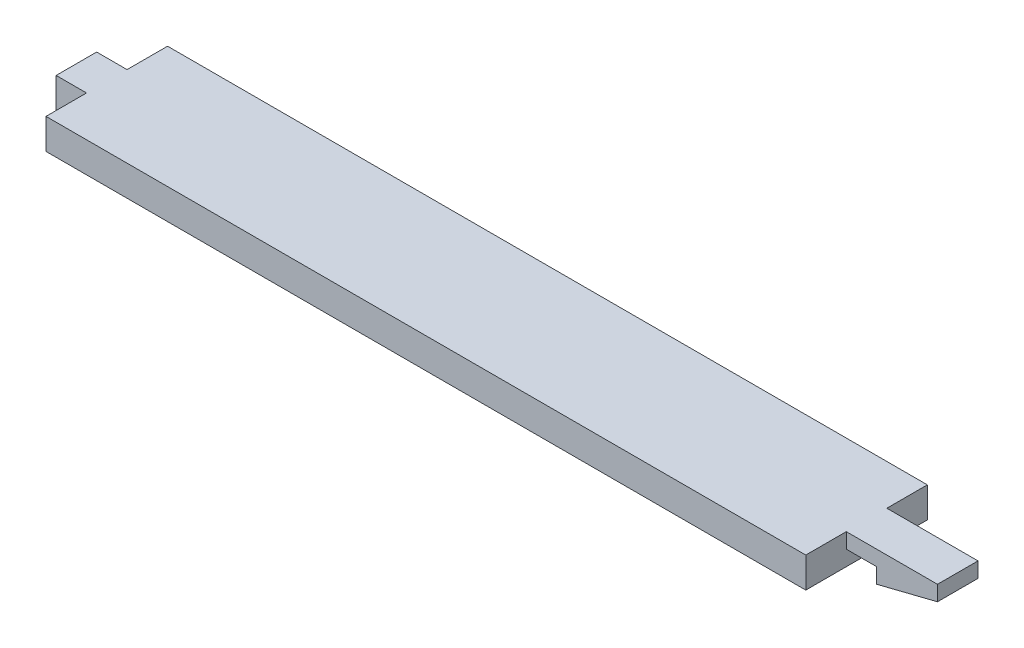
SolidWorks part; units mm, degrees
ref_plane "Front Plane" through (0, 0, 0) normal (0, 0, 1) x (1, 0, 0)
ref_plane "Top Plane" through (0, 0, 0) normal (0, 1, 0) x (1, 0, 0)
ref_plane "Right Plane" through (0, 0, 0) normal (1, 0, 0) x (0, 0, -1)
sketch "Sketch1" plane through (0, 0, 0) normal (0, 1, 0) x (1, 0, 0)
  line L1 (0, 0) -> (184.15, 0)
  line L2 (0, 0) -> (0, -25.4)
  line L3 (0, -25.4) -> (184.15, -25.4)
  line L4 (184.15, 0) -> (184.15, -25.4)
  dimension "D1" = 184.15
  dimension "D2" = 25.4
extrude "Boss-Extrude1" add sketch "Sketch1" along normal blind 6.35
sketch "Sketch4" plane through (0, 6.35, 0) normal (0, 1, 0) x (1, 0, 0)
  line L1 (0, 0) -> (6.35, 0)
  line L2 (0, 0) -> (0, -8.4667)
  line L3 (0, -8.4667) -> (6.35, -8.4667)
  line L4 (6.35, 0) -> (6.35, -8.4667)
  line L5 (0, -25.4) -> (6.35, -25.4)
  line L6 (0, -25.4) -> (0, -16.9333)
  line L7 (0, -16.9333) -> (6.35, -16.9333)
  line L8 (6.35, -25.4) -> (6.35, -16.9333)
  dimension "D1" = 6.35
  dimension "D2" = 8.4667
  dimension "D3" = 6.35
  dimension "D4" = 8.4667
extrude "Cut-Extrude1" cut sketch "Sketch4" against normal through all
sketch "Sketch5" plane through (0, 6.35, 0) normal (0, 1, 0) x (1, 0, 0)
  line L1 (184.15, -25.4) -> (165.1, -25.4)
  line L2 (184.15, -25.4) -> (184.15, -16.9333)
  line L3 (184.15, -16.9333) -> (165.1, -16.9333)
  line L4 (165.1, -25.4) -> (165.1, -16.9333)
  line L5 (184.15, 0) -> (165.1, 0)
  line L6 (184.15, 0) -> (184.15, -8.4667)
  line L7 (184.15, -8.4667) -> (165.1, -8.4667)
  line L8 (165.1, 0) -> (165.1, -8.4667)
  dimension "D1" = 8.4667
  dimension "D2" = 8.4667
  dimension "D3" = 19.05
  dimension "D4" = 19.05
extrude "Cut-Extrude2" cut sketch "Sketch5" against normal blind 6.35
sketch "Sketch6" plane through (0, 0, 0) normal (0, -1, 0) x (1, 0, 0)
  line L0 (184.15, 16.9333) -> (165.1, 16.9333) construction
  line L1 (165.1, 8.4667) -> (171.45, 8.4667)
  line L2 (165.1, 8.4667) -> (165.1, 16.9333)
  line L3 (165.1, 16.9333) -> (171.45, 16.9333)
  line L4 (171.45, 8.4667) -> (171.45, 16.9333)
  dimension "D1" = 6.35
extrude "Cut-Extrude3" cut sketch "Sketch6" against normal blind 3.175
chamfer "Chamfer3" distance 12.7 distance2 3.175 1 edges at (184.15, 0, 12.7) first distance on face at (177.8, 0, 12.7)
